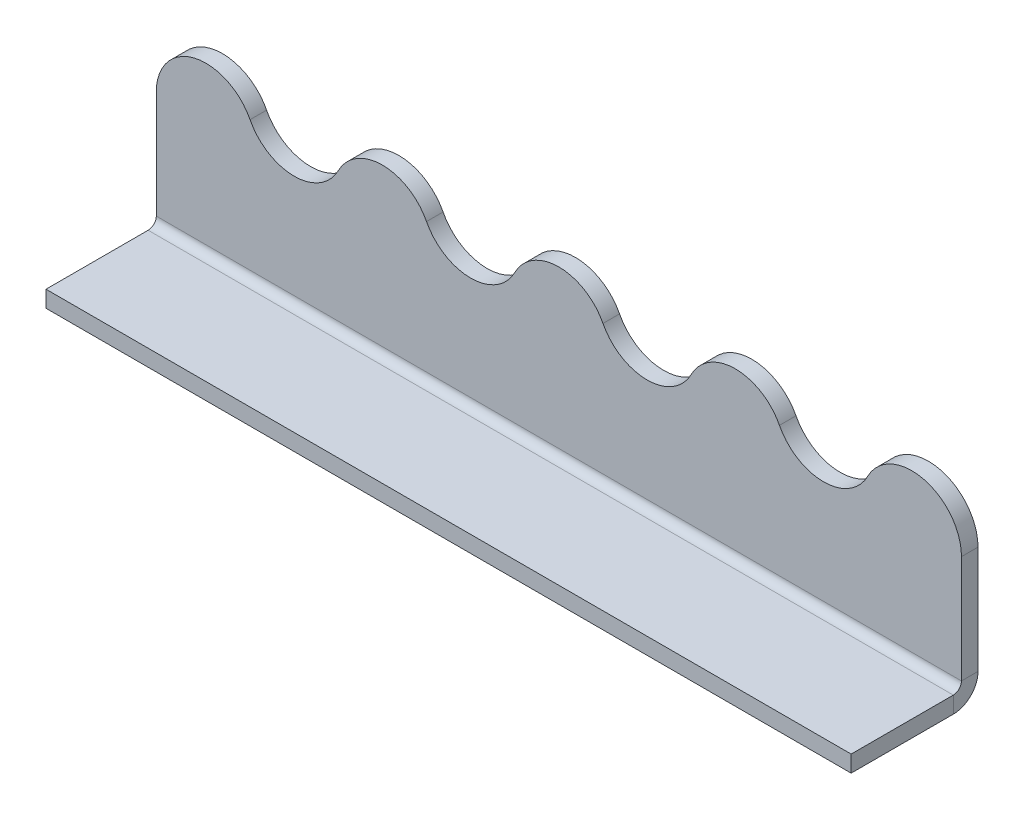
SolidWorks part; units mm, degrees
note: The reader was unsure of these and kept them because the rebuilt part matched: flange length of "Ребро-кромка1".
material "AISI 1020"
ref_plane "Спереди" through (0, 0, 0) normal (0, 0, 1) x (1, 0, 0)
ref_plane "Сверху" through (0, 0, 0) normal (0, 1, 0) x (1, 0, 0)
ref_plane "Справа" through (0, 0, 0) normal (1, 0, 0) x (0, 0, -1)
sketch "Эскиз1" plane through (0, 0, 0) normal (0, 0, 1) x (1, 0, 0)
  line L0 (0, -1046.3752) -> (0, 51272.3838) construction
  line L1 (-36.5, 0) -> (36.5, 0)
  line L2 (-1000.0057, 15) -> (48999.9943, 15) construction
  line L3 (-2340.8699, 12.5616) -> (47659.1301, 12.5616) construction
  line L4 (36.5, 10.5) -> (36.5, 0)
  line L5 (-36.5, 10.5) -> (-36.5, 0)
  arc A0 (-4, 12.5616) -> (4, 12.5616) centre (0, 10.5) cw
  arc A1 (4, 12.5616) -> (12, 12.5616) centre (8, 14.6231) ccw
  arc A2 (12, 12.5616) -> (20, 12.5616) centre (16, 10.5) cw
  arc A3 (20, 12.5616) -> (28, 12.5616) centre (24, 14.6231) ccw
  arc A4 (28, 12.5616) -> (36.5, 10.5) centre (32, 10.5) cw
  arc A5 (-28, 12.5616) -> (-36.5, 10.5) centre (-32, 10.5) ccw
  arc A6 (-20, 12.5616) -> (-28, 12.5616) centre (-24, 14.6231) cw
  arc A7 (-12, 12.5616) -> (-20, 12.5616) centre (-16, 10.5) ccw
  arc A8 (-4, 12.5616) -> (-12, 12.5616) centre (-8, 14.6231) cw
  point P27 (0, 0)
  dimension "D1" = 73
  dimension "D2" = 15
base flange "Базовая кромка1" sketch "Эскиз1" thickness 1.5 reverse thickness direction no parameters "D1"=0.74
edge flange "Ребро-кромка1" sketch "Эскиз8" flange angle 90 flange length 10 flange position material outside bend radius 0.74 thickness 1.5 relief obround parameters "D6"=10
sketch "Эскиз8" plane through (0, 0, 0) normal (0, -1, 0) x (1, 0, 0)
  line L0 (-36.5, 0) -> (36.5, 0) construction
  line L1 (-36.5, 0) -> (36.5, 0)
  line L2 (-36.5, 0) -> (-36.5, 10)
  line L3 (-36.5, 10) -> (36.5, 10)
  line L4 (36.5, 10) -> (36.5, 0)
bend "EdgeBend1" bend radius 0.74 bend angle 90 parameters "D5"=1
sketch "Сгиб-Линии1" [suppressed] plane through (0, 0, 0) normal (0, 1, 0) x (1, 0, 0)
sketch "Граничная рамка1" [suppressed] plane through (0, 0, 0) normal (0, 1, 0) x (1, 0, 0)
sheet metal parameters "Листовой металл3" thickness 1.5 parameters "D1"=0.74
flat pattern "Развертка3" [suppressed]
sketch "Сгиб-Линии2" plane through (0, 0, 0) normal (0, 1, 0) x (1, 0, 0)
sketch "Граничная рамка2" [suppressed] plane through (0, 0, 0) normal (0, 1, 0) x (1, 0, 0)
sheet metal parameters "Листовой металл4" thickness 1.5 parameters "D1"=0.74
flat pattern "Развертка3"
sketch "Сгиб-Линии2" plane through (0, 0, 0) normal (0, 0, 1) x (1, 0, 0)
  line L0 (-36.5, -0.4302) -> (36.5, -0.4302) construction
  line L1 (-36.5, -0.4302) -> (36.5, -0.4302) construction
sketch3d "Граничная рамка2" [suppressed]
  line L0 (-4.5, 4.5, 0) -> (68.5, 4.4998, 0) construction
  line L1 (-4.5, -21.3603, 0) -> (68.5, -21.3605, 0) construction
  line L2 (-4.5, 4.5, 0) -> (-4.5, -21.3603, 0) construction
  line L3 (68.5, 4.4998, 0) -> (68.5, -21.3605, 0) construction
bend of the flat pattern "Плоское состояние-<EdgeBend1>1"
